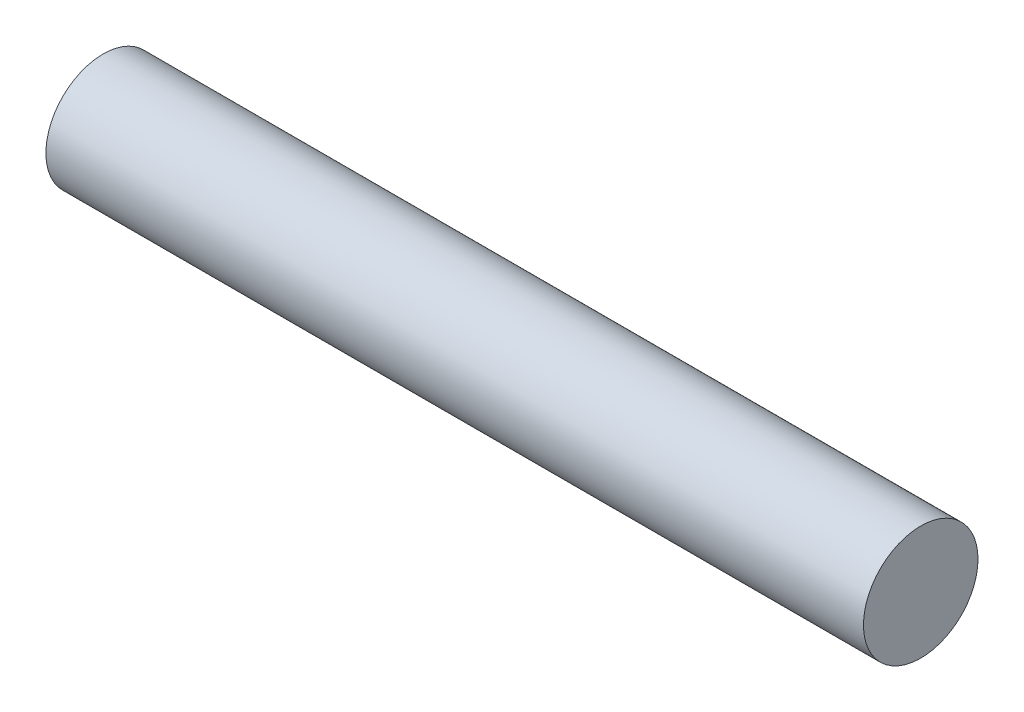
SolidWorks part; units mm, degrees
ref_plane "Front Plane" through (0, 0, 0) normal (0, 0, 1) x (1, 0, 0)
ref_plane "Top Plane" through (0, 0, 0) normal (0, 1, 0) x (1, 0, 0)
ref_plane "Right Plane" through (0, 0, 0) normal (1, 0, 0) x (0, 0, -1)
sketch "Sketch1" plane through (0, 0, 0) normal (1, 0, 0) x (0, 0, -1)
  circle A0 centre (0, 0) radius 22.2928
  dimension "D1" = 44.5856
extrude "Boss-Extrude1" add sketch "Sketch1" against normal blind 159.131 and the other way blind 159.131
